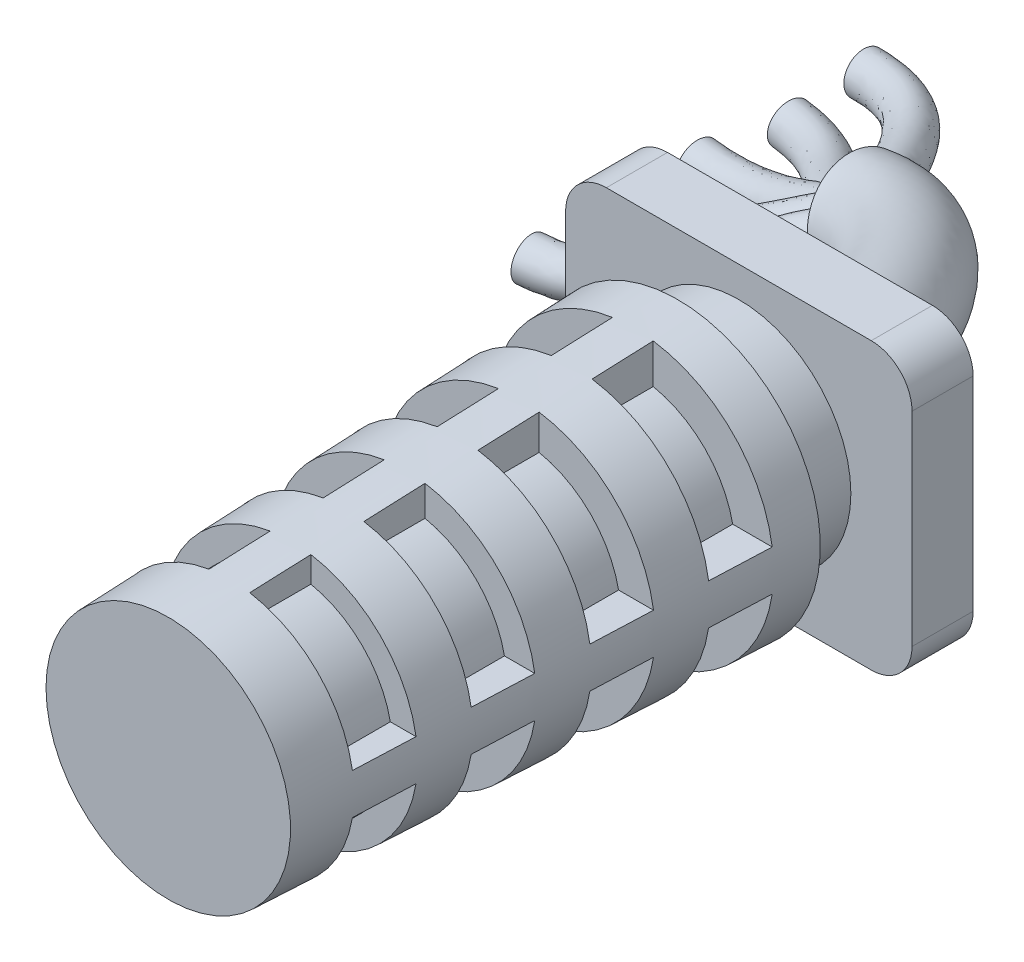
SolidWorks part; units mm, degrees
material "POLYURETHANE (11671)"
ref_plane "Front Plane" through (0, 0, 0) normal (0, 0, 1) x (1, 0, 0)
ref_plane "Top Plane" through (0, 0, 0) normal (0, 1, 0) x (1, 0, 0)
ref_plane "Right Plane" through (0, 0, 0) normal (1, 0, 0) x (0, 0, -1)
sketch "Sketch1" plane through (0, 0, 0) normal (0, 0, 1) x (1, 0, 0)
  line L1 (4.25, -3.5) -> (-4.25, -3.5)
  line L2 (4.25, -3.5) -> (4.25, 3.5)
  line L3 (4.25, 3.5) -> (-4.25, 3.5)
  line L4 (-4.25, -3.5) -> (-4.25, 3.5)
  line L5 (4.25, -3.5) -> (-4.25, 3.5) construction
  line L6 (4.25, 3.5) -> (-4.25, -3.5) construction
  circle A0 centre (0, 0) radius 1.8
  point P0 (0, 0)
  dimension "D3" = 3.6
  dimension "D1" = 8.5
  dimension "D2" = 7
extrude "Boss-Extrude1" add sketch "Sketch1" along normal blind 1.5
sketch "Sketch2" plane through (0, 0, 1.5) normal (0, 0, 1) x (1, 0, 0)
  circle A0 centre (0, 0) radius 2.75
  circle M5 centre (0, 0) radius 1.8
  dimension "D1" = 5.5
extrude "Boss-Extrude2" add sketch "Sketch2" along normal blind 1.5 contours A0 M5 region at (-2.6722, 0, 1.5)
sketch "Sketch4" plane through (0, 0, 0) normal (0, 1, 0) x (1, 0, 0)
  line L0 (-1.8, -3) -> (-3.5, -3)
  line L1 (-3.5, -3) -> (-3, -15.5)
  line L2 (-3, -15.5) -> (-1.8, -15.5)
  line L3 (-1.8, -15.5) -> (-1.8, -3)
  line L4 (0, 0) -> (0, -4.1714) construction
  line L5 (4.25, 0) -> (-4.25, 0) construction
  dimension "D1" = 7
  dimension "D2" = 6
  dimension "D3" = 15.5
revolve "Revolve1" add sketch "Sketch4" angle 360 about L4
fillet "Fillet1" radius 1 4 edges at (4.25, -3.5, 0.75) (-4.25, -3.5, 0.75) (-4.25, 3.5, 0.75) (4.25, 3.5, 0.75)
sketch "Sketch5" plane through (0, 0, 15.5) normal (0, 0, 1) x (1, 0, 0)
  line L0 (-0.5, 2.4495) -> (-0.5, 3.7498)
  line L1 (-0.5, 3.7498) -> (-4.5796, 3.7498)
  line L2 (-4.5796, 3.7498) -> (-4.5796, 0.5)
  line L3 (-4.5796, 0.5) -> (-2.4495, 0.5)
  line L4 (-0.8846, 0) -> (0, 0) construction
  line L5 (0, 0) -> (0, 1.276) construction
  line L6 (0.5, 4.5796) -> (0.5, 2.4495)
  line L7 (3.7498, 4.5796) -> (0.5, 4.5796)
  line L8 (3.7498, 0.5) -> (3.7498, 4.5796)
  line L9 (2.4495, 0.5) -> (3.7498, 0.5)
  line L10 (4.5796, -0.5) -> (2.4495, -0.5)
  line L11 (4.5796, -3.7498) -> (4.5796, -0.5)
  line L12 (0.5, -3.7498) -> (4.5796, -3.7498)
  line L13 (0.5, -2.4495) -> (0.5, -3.7498)
  line L14 (-0.5, -4.5796) -> (-0.5, -2.4495)
  line L15 (-3.7498, -4.5796) -> (-0.5, -4.5796)
  line L16 (-3.7498, -0.5) -> (-3.7498, -4.5796)
  line L17 (-2.4495, -0.5) -> (-3.7498, -0.5)
  circle A0 centre (0, 0) radius 2.5
  circle M8 centre (0, 0) radius 3
  dimension "D1" = 5
  dimension "D2" = 1
  dimension "D3" = 1
  dimension "D4" = 4
extrude "Cut-Extrude1" cut sketch "Sketch5" against normal blind 1.5 from offset 1.5 contours L2 L3 L0 L1 M8 | L9 L8 L7 L6 M8 | L13 L12 L11 L10 M8 | L17 L16 L15 L14 M8 | A0 L0 L3 M8 | A0 L17 L14 M8 | A0 L13 L10 M8 | A0 L9 L6 M8 region at (-1.8353, 1.8353, 15.5) region at (-3.0488, 2.4325, 15.5) region at (1.8353, 1.8353, 15.5) region at (2.4325, 3.0488, 15.5) region at (-1.8353, -1.8353, 15.5) region at (-2.4325, -3.0488, 15.5) region at (1.8353, -1.8353, 15.5) region at (3.0488, -2.4325, 15.5) offset against normal yes
pattern_linear "LPattern1" count 4 spacing 2.8 along (0, 0, -1) of "Cut-Extrude1"
sketch "Sketch6" plane through (0, 0, 0) normal (0, 0, -1) x (-1, 0, 0)
  circle A0 centre (0, 0) radius 1.8
extrude "Boss-Extrude3" add sketch "Sketch6" against normal through all
sketch3d "3DSketch1"
  spline S0 degree 3 poles (0, 0, 0) (-0.1483, -0.1183, -3.047) (-2.8532, -1.3266, -6.202) (-4.7664, -1.7486, -6.2609) knots 0 0 0 0 1 1 1 1
sweep "MainCable" add path "3DSketch1" circular profile diameter 2.5 parameters "D3"=2.5
sketch3d "3DSketch2"
  spline S0 degree 3 poles (-4.4291, -1.7486, -6.5982) (-5.9632, -2.3121, -7.2055) (-6.3645, -2.989, -10.6349) (-9.0964, -3.0693, -10.6818) knots 0 0 0 0 1 1 1 1
sweep "PWR" add path "3DSketch2" circular profile diameter 1 parameters "D3"=1
sketch3d "3DSketch3"
  spline S0 degree 3 poles (-4.7664, -1.7486, -6.2609) (-6.1965, -2.2557, -6.4867) (-7.1179, -3.1376, -8.541) (-8.9348, -3.0548, -8.6683) knots 0 0 0 0 1 1 1 1
sweep "DM" add path "3DSketch3" circular profile diameter 1 parameters "D3"=1
sketch3d "3DSketch4"
  spline S0 degree 3 poles (-4.7664, -1.7486, -6.2609) (-6.1912, -2.3178, -6.4005) (-7.2679, -3.1344, -6.5924) (-9.2016, -3.0288, -6.6837) knots 0 0 0 0 1 1 1 1
sweep "DP" add path "3DSketch4" circular profile diameter 1 parameters "D3"=1
sketch3d "3DSketch5"
  spline S0 degree 3 poles (-4.7664, -1.7486, -6.2609) (-6.2596, -2.403, -5.9887) (-6.8923, -3.0488, -4.6952) (-9.1832, -3.0226, -4.667) knots 0 0 0 0 1 1 1 1
sweep "GND" add path "3DSketch5" circular profile diameter 1 parameters "D3"=1
sketch3d "3DSketch6"
  spline S0 degree 3 poles (-4.5347, -1.7411, -5.7789) (-6.3166, -2.266, -4.7311) (-6.5831, -3.0529, -2.8014) (-9.1901, -2.996, -2.5489) knots 0 0 0 0 1 1 1 1
sweep "Shield" add path "3DSketch6" circular profile diameter 1 parameters "D3"=1
